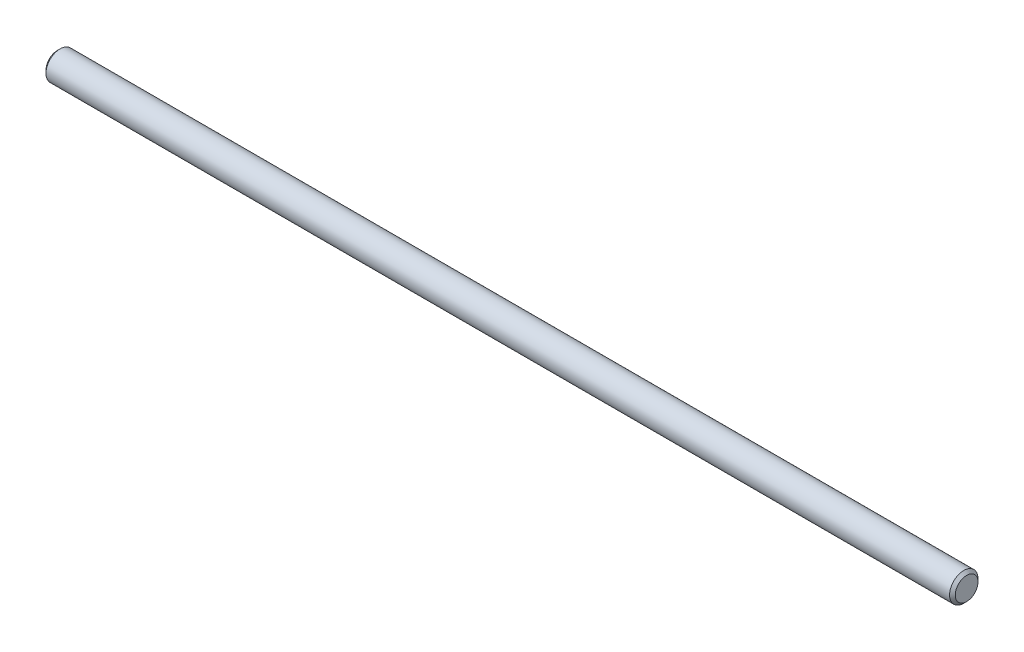
SolidWorks part; units mm, degrees
material "AISI 316 Stainless Steel Sheet (SS)"
ref_plane "Front" through (0, 0, 0) normal (0, 0, 1) x (1, 0, 0)
ref_plane "Top" through (0, 0, 0) normal (0, 1, 0) x (1, 0, 0)
ref_plane "Right" through (0, 0, 0) normal (1, 0, 0) x (0, 0, -1)
sketch "Sketch1" plane through (0, 0, 0) normal (0, 0, 1) x (1, 0, 0)
  line L0 (-101.6, 0) -> (101.6, 0) construction
  line L1 (101.6, 3.175) -> (101.6, -3.175) construction
  line L2 (-101.6, 3.175) -> (-101.6, -3.175) construction
sketch "Sketch2" plane through (0, 0, 0) normal (1, 0, 0) x (0, 0, -1)
  line L0 (3.175, 0) -> (-3.175, 0) construction
  circle A0 centre (0, 0) radius 3.175
  point P6 (0, 0)
  dimension "D1" = 6.35
extrude "Extrude1" add sketch "Sketch2" against normal up to vertex (101.6 mm away) and the other way up to vertex (101.6 mm away) up to point (-101.6, 3.175, 0) other way up to point (101.6, 3.175, 0)
chamfer "Chamfer1" distance 0.635 angle 45 2 edges at (101.6, 0, -3.175) (-101.6, 0, -3.175)
ref_axis "Center Axis1" through (-12.2237, 0, 0) along (1, 0, 0)
ref_plane "Contact Plane1" through (-101.6, 0, 0) normal (1, 0, 0) x (0, 0, -1)
ref_plane "Contact Plane2" through (101.6, 0, 0) normal (1, 0, 0) x (0, 0, -1)
equation "\"D1@Chamfer1\" = \"Diameter@Sketch1\"*.1"
equation "\"D1@Sketch2\"=\"Diameter@Sketch1\""
